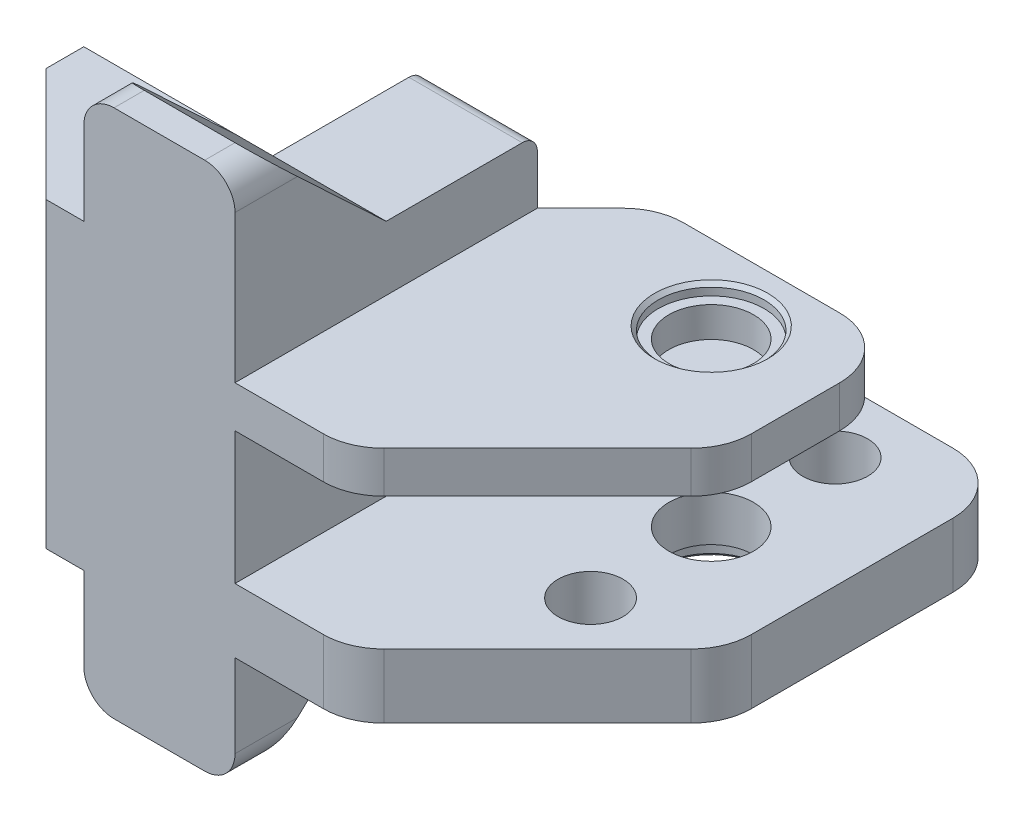
SolidWorks part; units mm, degrees
ref_plane "Front Plane" through (0, 0, 0) normal (0, 0, 1) x (1, 0, 0)
ref_plane "Top Plane" through (0, 0, 0) normal (0, 1, 0) x (1, 0, 0)
ref_plane "Right Plane" through (0, 0, 0) normal (1, 0, 0) x (0, 0, -1)
sketch "Sketch1" plane through (0, 0, 0) normal (0, 1, 0) x (1, 0, 0)
  line L1 (0, 0) -> (40, 0)
  line L2 (0, 0) -> (0, 40)
  line L3 (0, 40) -> (40, 40)
  line L4 (40, 0) -> (40, 40)
extrude "Boss-Extrude1" add sketch "Sketch1" along normal blind 40
sketch "Sketch2" plane through (0, 40, 0) normal (0, 1, 0) x (1, 0, 0)
  line L0 (0, 40) -> (25, 40)
  line L1 (40, 40) -> (0, 40) construction
  line L2 (25, 40) -> (25, 20)
  line L3 (25, 20) -> (0, 20)
  line L4 (0, 40) -> (0, 0) construction
  line L5 (0, 20) -> (0, 40)
extrude "Cut-Extrude1" cut sketch "Sketch2" against normal blind 40
chamfer "Chamfer1" distance 15 angle 45 1 edges at (0, 20, 0)
sketch "Sketch3" plane through (0, 0, 0) normal (0, 0, 1) x (1, 0, 0)
  line L4 (0, 0) -> (0, 40) construction
  line L5 (0, 10) -> (0, 15)
  line L6 (0, 15) -> (15, 15)
  line L7 (15, 15) -> (15, 5)
  line L8 (15, 5) -> (0, 5)
  line L9 (0, 5) -> (0, 10)
  line L11 (0, 30) -> (0, 25)
  line L12 (0, 25) -> (15, 25)
  line L13 (15, 25) -> (15, 35)
  line L14 (15, 35) -> (0, 35)
  line L15 (0, 35) -> (0, 30)
extrude "Cut-Extrude2" cut sketch "Sketch3" against normal blind 15
chamfer "Chamfer2" distance 4 angle 45 4 edges at (15, 5, -7.5) (15, 15, -7.5) (15, 35, -7.5) (15, 25, -7.5)
sketch "Sketch4" plane through (0, 0, -15) normal (0, 0, 1) x (1, 0, 0)
  line L0 (0, 30) -> (8, 30)
  line L1 (0, 35) -> (0, 25) construction
  line L2 (0, 10) -> (8, 10)
  line L3 (0, 15) -> (0, 5) construction
  circle A0 centre (8, 30) radius 2.6
  circle A1 centre (8, 10) radius 2.6
extrude "Cut-Extrude3" cut sketch "Sketch4" against normal blind 17
sketch "Sketch5" plane through (0, 0, -40) normal (0, 0, -1) x (-1, 0, 0)
  line L0 (-40, 20) -> (-85, 20) construction
  line L1 (-40, 40) -> (-40, 0) construction
  line L5 (-80, 8.5) -> (-40, 8.5)
  line L11 (-40, 20) -> (-40, 26)
  line L12 (-40, 40) -> (-40, 0) construction
  line L13 (-40, 26) -> (-80, 26)
  line L14 (-40, 26) -> (-40, 31.5)
  line L15 (-40, 31.5) -> (-80, 31.5)
  line L16 (-80, 31.5) -> (-80, 26)
  line L17 (-40, 8.5) -> (-40, 0)
  line L18 (-40, 0) -> (-80, 0)
  line L19 (-80, 0) -> (-80, 8.5)
  dimension "D1" = 11.5
  dimension "D2" = 6
  dimension "8" = 8.5
extrude "Boss-Extrude2" add sketch "Sketch5" along normal blind 8 and the other way blind 40
sketch "Sketch10" plane through (40, 0, 0) normal (1, 0, 0) x (0, 0, -1)
  line L0 (40, 20) -> (36, 20)
  line L1 (40, 25) -> (40, 15) construction
  line L2 (36, 15) -> (36, 25)
  line L3 (40, 25) -> (0, 25) construction
  line L4 (36, 25) -> (22, 25)
  line L5 (22, 25) -> (22, 15)
  line L6 (36, 15) -> (22, 15)
  point P10 (22, 20)
  dimension "D1" = 4
  dimension "D2" = 14
extrude "Cut-Extrude5" cut sketch "Sketch10" against normal blind 26
chamfer "Chamfer5" distance 8 angle 45 3 edges at (40, 28.75, -48) (40, 26, -44) (40, 31.5, -44)
sketch "Sketch8" plane through (0, 32, 0) normal (0, 1, 0) x (1, 0, 0)
  line L0 (80, 48) -> (80, 38) construction
  line L2 (80, 48) -> (80, 0) construction
  line L3 (80, 38) -> (65, 38) construction
  circle A1 centre (65, 38) radius 5.6
extrude "Cut-Extrude4" cut sketch "Sketch8" against normal blind 34
sketch "Sketch9" plane through (40, 0, 0) normal (1, 0, 0) x (0, 0, -1)
  line L0 (0, 40) -> (0, 55)
  line L1 (0, 40) -> (20, 40)
  line L2 (0, 40) -> (40, 40) construction
  line L4 (0, 0) -> (0, -15)
  line L5 (0, 0) -> (20, 0)
  line L7 (0, 55) -> (4, 55)
  line L8 (4, 55) -> (20, 40)
  line L9 (0, -15) -> (4, -15)
  line L10 (4, -15) -> (20, 0)
extrude "Boss-Extrude3" add sketch "Sketch9" against normal blind 20
fillet "Fillet3" radius 4 4 edges at (20, -15, -2) (40, -15, -2) (20, 55, -2) (40, 55, -2)
fillet "Fillet4" radius 2 2 edges at (32.5, 40, -40) (32.5, 0, -40)
sketch "Sketch12" plane through (0, 31.5, 0) normal (0, 1, 0) x (1, 0, 0)
  circle A1 centre (65, 38) radius 7
extrude "Cut-Extrude6" cut sketch "Sketch12" against normal blind 1.5
sketch "Sketch13" plane through (0, 0, 0) normal (0, -1, 0) x (1, 0, 0)
  circle A1 centre (65, -38) radius 7
extrude "Cut-Extrude7" cut sketch "Sketch13" against normal blind 2.5
chamfer "Chamfer7" distance 25 angle 45 2 edges at (80, 4.25, 0) (80, 28.75, 0)
fillet "Fillet6" radius 8 6 edges at (55, 4.25, 0) (55, 28.75, 0) (80, 28.75, -25) (80, 4.25, -25) (80, 28.75, -48) (48, 28.75, -48)
chamfer "Chamfer8" distance 2 distance2 10 1 edges at (40, 20, -36)
fillet "Fillet7" radius 2 6 edges at (27.5, 25, -36) (27.5, 15, -36) (32.5, 15, -22) (32.5, 25, -22) (35, 25, -37) (35, 15, -37)
sketch "Sketch14" plane through (0, 0, -48) normal (0, 0, -1) x (-1, 0, 0)
  line L0 (-80, 8.5) -> (-40, 8.5)
  line L1 (-80, 8.5) -> (-40, 8.5) construction
  line L2 (-40, 8.5) -> (-40, 0)
  line L3 (-40, 0) -> (-80, 0)
  line L4 (-80, 0) -> (-80, 8.5)
extrude "Boss-Extrude4" add sketch "Sketch14" along normal blind 15
sketch "Sketch15" plane through (0, 0, 0) normal (0, -1, 0) x (1, 0, 0)
  circle A0 centre (65.2609, -54.1305) radius 4.3
  circle A1 centre (65.169, -21.8682) radius 4.3
extrude "Cut-Extrude8" cut sketch "Sketch15" against normal blind 10
fillet "Fillet8" radius 8 2 edges at (40, 4.25, -63) (80, 4.25, -63)
chamfer "Chamfer10" distance 0.5 angle 45 2 edges at (58, 31.5, -38) (65, 0, -45)
